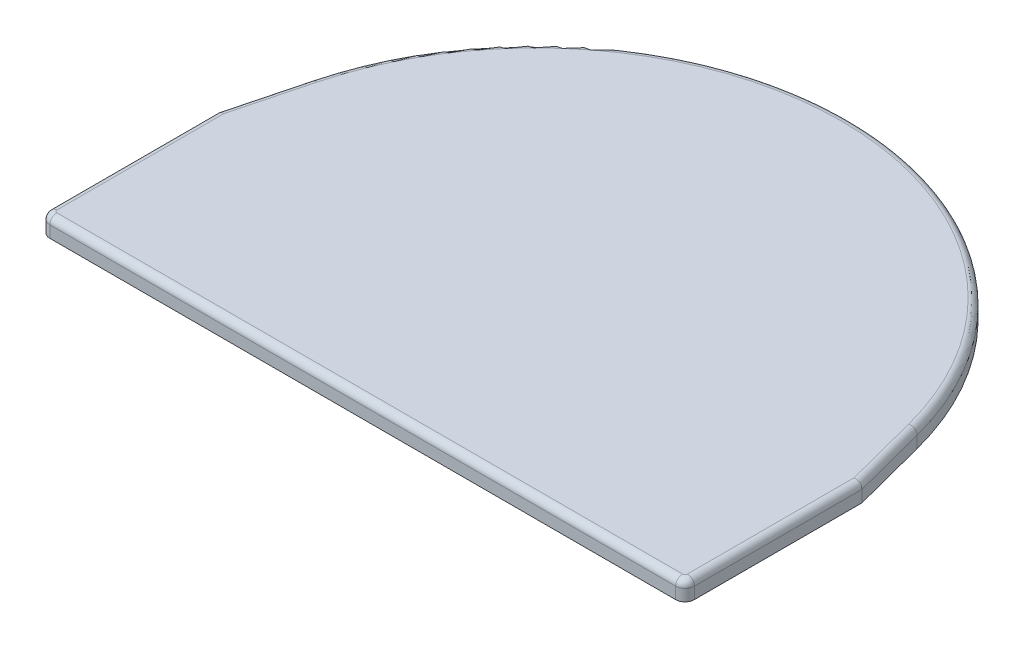
SolidWorks part; units mm, degrees
ref_plane "Front Plane" through (0, 0, 0) normal (0, 0, 1) x (1, 0, 0)
ref_plane "Top Plane" through (0, 0, 0) normal (0, 1, 0) x (1, 0, 0)
ref_plane "Right Plane" through (0, 0, 0) normal (1, 0, 0) x (0, 0, -1)
sketch "Sketch2" plane through (0, 0, 0) normal (0, 1, 0) x (1, 0, 0)
  line L0 (-121.6565, -77.8034) -> (-59.6565, -77.8034) construction
  line L1 (-121.6565, -70.3034) -> (-59.6565, -70.3034) construction
  line L2 (-59.6565, -77.8034) -> (-59.6565, -62.8034) construction
  line L3 (-90.6565, -62.8034) -> (-90.6565, -77.8034) construction
  line L4 (-119.6887, -55.2451) -> (-121.6565, -62.8034) construction
  line L5 (-121.6565, -62.8034) -> (-121.6565, -77.8034) construction
  line L6 (-61.6242, -55.2451) -> (-59.6565, -62.8034) construction
  line L7 (-104.935, -77.8034) -> (-104.935, -70.3034) construction
  line L13 (-62.1081, -55.3711) -> (-60.1565, -62.8674)
  line L14 (-60.1565, -77.3034) -> (-60.1565, -62.8674)
  line L15 (-121.1565, -77.3034) -> (-60.1565, -77.3034)
  line L16 (-121.1565, -62.8674) -> (-121.1565, -77.3034)
  line L17 (-119.2049, -55.3711) -> (-121.1565, -62.8674)
  arc A0 (-119.6887, -55.2451) -> (-61.6242, -55.2451) centre (-90.6565, -62.8034) cw construction
  arc A2 (-119.2049, -55.3711) -> (-62.1081, -55.3711) centre (-90.6565, -62.8034) cw
  dimension "D2" = 30
  dimension "D1" = 15
  dimension "D3" = 7.5
  dimension "D4" = 62
  dimension "D5" = 0.5
extrude "Boss-Extrude1" add sketch "Sketch2" along normal blind 2.75
sketch "Sketch12" plane through (0, 0, 77.3034) normal (0, 0, 1) x (1, 0, 0)
  line L1 (-105.6565, 1.5) -> (-75.6565, 1.5)
  line L2 (-105.6565, 1.5) -> (-105.6565, 0)
  line L3 (-105.6565, 0) -> (-75.6565, 0)
  line L4 (-75.6565, 1.5) -> (-75.6565, 0)
  line L5 (-90.6565, 2.75) -> (-90.6565, 1.5) construction
  line L7 (-62.1081, 2.75) -> (-119.2049, 2.75) construction
  line L8 (-105.6565, 2.75) -> (-105.6565, 0.75) construction
  dimension "D1" = 2
  dimension "D2" = 30
  dimension "D3" = 1.5
extrude "Boss-Extrude4" add sketch "Sketch12" along normal blind 1
fillet "Fillet7" radius 0.75 2 edges at (-75.6565, 0.75, 78.3034) (-105.6565, 0.75, 78.3034)
fillet "Fillet8" radius 0.75 10 edges at (-105.4368, 0, 78.0837) (-75.8761, 0, 78.0837) (-75.6565, 1.5, 77.4284) (-75.8761, 1.5, 78.0837) (-105.6565, 1.5, 77.4284) (-105.4368, 1.5, 78.0837) (-90.6565, 0, 78.3034) (-90.6565, 1.5, 78.3034)
sketch "Sketch13" plane through (0, 2.75, 0) normal (0, 1, 0) x (1, 0, 0)
  line L0 (-121.6565, -77.8034) -> (-59.6565, -77.8034) construction
  line L1 (-121.6565, -70.3034) -> (-59.6565, -70.3034) construction
  line L2 (-59.6565, -77.8034) -> (-59.6565, -62.8034) construction
  line L3 (-90.6565, -62.8034) -> (-90.6565, -77.8034) construction
  line L4 (-119.6887, -55.2451) -> (-121.6565, -62.8034) construction
  line L5 (-121.6565, -62.8034) -> (-121.6565, -77.8034) construction
  line L6 (-61.6242, -55.2451) -> (-59.6565, -62.8034) construction
  line L7 (-104.935, -77.8034) -> (-104.935, -70.3034) construction
  line L13 (-58.2371, -54.3633) -> (-56.1565, -62.3553)
  line L14 (-56.1565, -81.3034) -> (-56.1565, -62.3553)
  line L15 (-125.1565, -81.3034) -> (-56.1565, -81.3034)
  line L16 (-125.1565, -62.3553) -> (-125.1565, -81.3034)
  line L17 (-123.0758, -54.3633) -> (-125.1565, -62.3553)
  arc A0 (-119.6887, -55.2451) -> (-61.6242, -55.2451) centre (-90.6565, -62.8034) cw construction
  arc A2 (-123.0758, -54.3633) -> (-58.2371, -54.3633) centre (-90.6565, -62.8034) cw
  dimension "D2" = 30
  dimension "D1" = 15
  dimension "D3" = 7.5
  dimension "D4" = 62
  dimension "D5" = 3.5
extrude "Boss-Extrude5" add sketch "Sketch13" along normal blind 2
sketch "Sketch14" plane through (0, 0, 0) normal (0, 0, 1) x (1, 0, 0)
  line L1 (-81.1565, 1.5) -> (-100.1565, 1.5)
  line L2 (-81.1565, 1.5) -> (-81.1565, 0)
  line L3 (-81.1565, 0) -> (-100.1565, 0)
  line L4 (-100.1565, 1.5) -> (-100.1565, 0)
  line L5 (-90.6565, 2.75) -> (-90.6565, 1.5) construction
  line L6 (-123.0758, 2.75) -> (-58.2371, 2.75) construction
  line L7 (-100.1565, 2.75) -> (-100.1565, 0.75) construction
  line L8 (-119.2049, 2.75) -> (-62.1081, 2.75) construction
  dimension "D1" = 19
  dimension "D2" = 2
  dimension "D3" = 1.5
wrap "Wrap4" sketch "Sketch14" wrap type emboss source sketch "Sketch14" thickness 1 face at (-90.6565, 1.375, 44.3372) parameters "D1"=1
fillet "Fillet12" radius 1 2 edges at (-125.1565, 3.75, 81.3034) (-56.1565, 3.75, 81.3034)
fillet "Fillet14" radius 2 2 edges at (-121.1565, 1.375, 77.3034) (-60.1565, 1.375, 77.3034)
fillet "Fillet19" radius 0.75 2 edges at (-81.0033, 0.75, 33.8713) (-100.3096, 0.75, 33.8713)
fillet "Fillet20" radius 0.75 6 edges at (-100.0312, 1.5, 34.7058) (-100.0245, 1.5, 34.0107) (-81.2818, 1.5, 34.7058) (-81.2885, 1.5, 34.0107) (-90.6565, 0, 32.3034) (-90.6565, 1.5, 32.3034)
fillet "Fillet21" radius 0.75 8 edges at (-57.1968, 4.75, 58.3593) (-56.1565, 4.75, 71.3293) (-56.4494, 4.75, 81.0105) (-90.6565, 4.75, 29.3034) (-124.1162, 4.75, 58.3593) (-90.6565, 4.75, 81.3034) (-124.8636, 4.75, 81.0105) (-125.1565, 4.75, 71.3293)
sketch "Sketch16" plane through (0, 0, 0) normal (0, -1, 0) x (1, 0, 0)
  line L0 (-90.6565, 77.5534) -> (-90.6565, 33.0534) construction
  line L1 (-76.4065, 77.5534) -> (-104.9065, 77.5534) construction
  line L2 (-113.1565, 67.3034) -> (-68.1565, 67.3034)
  line L3 (-76.4065, 77.3034) -> (-62.1565, 77.3034) construction
  arc A0 (-99.3578, 34.3543) -> (-81.9551, 34.3543) centre (-90.6565, 62.8034) ccw construction
  arc A1 (-113.1565, 67.3034) -> (-68.1565, 67.3034) centre (-90.6565, 67.3034) ccw
  dimension "D1" = 45
  dimension "D2" = 10
extrude "Cut-Extrude1" cut sketch "Sketch16" against normal blind 3
fillet "Fillet22" radius 1 2 edges at (-90.6565, 3, 67.3034) (-90.6565, 3, 44.8034)
fillet "Fillet23" radius 1 2 edges at (-90.6565, 0, 44.8034) (-90.6565, 0, 67.3034)
fillet "Fillet24" radius 0.75 10 edges at (-111.9487, 0, 42.3855) (-120.1807, 0, 59.1192) (-121.1565, 0, 69.0854) (-120.5707, 0, 76.7176) (-60.7423, 0, 76.7176) (-60.1565, 0, 69.0854) (-61.1323, 0, 59.1192) (-69.3642, 0, 42.3855)
